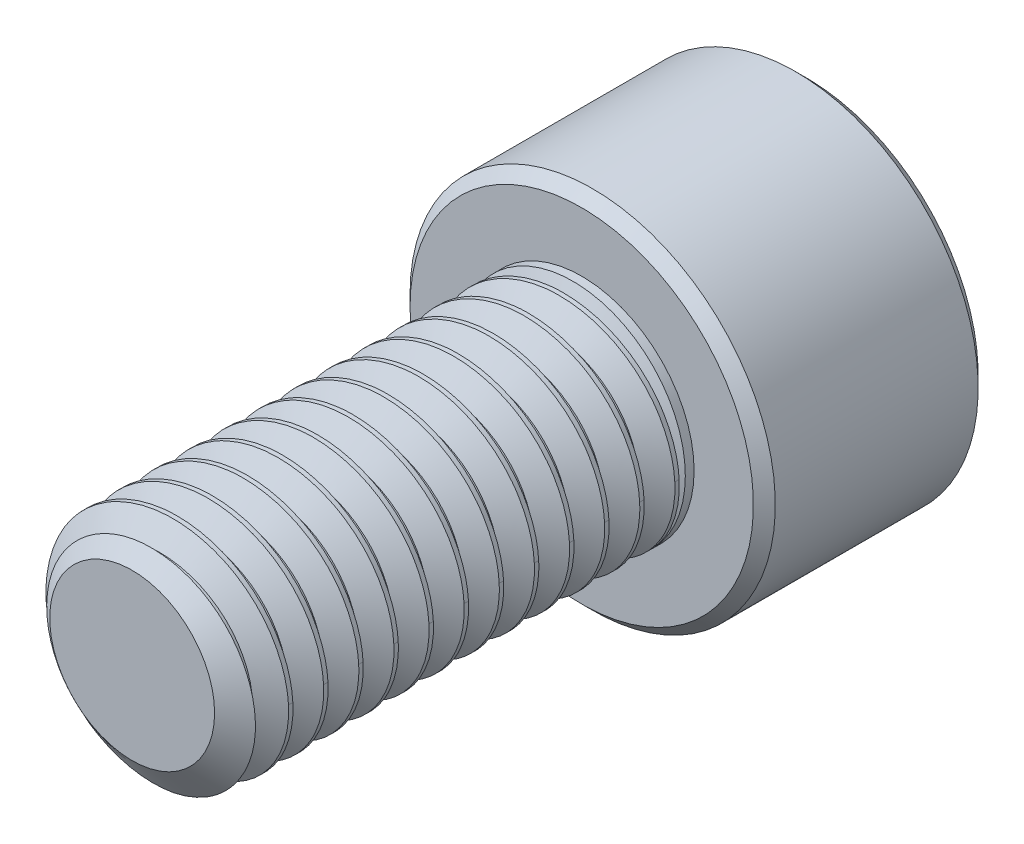
SolidWorks part; units mm, degrees
ref_plane "Front Plane" through (0, 0, 0) normal (0, 0, 1) x (1, 0, 0)
ref_plane "Top Plane" through (0, 0, 0) normal (0, 1, 0) x (1, 0, 0)
ref_plane "Right Plane" through (0, 0, 0) normal (1, 0, 0) x (0, 0, -1)
sketch "Sketch1" plane through (0, 0, 0) normal (0, 0, 1) x (1, 0, 0)
  circle A0 centre (0, 0) radius 4
  dimension "OD" = 8
extrude "Extrude1" add sketch "Sketch1" against normal blind 16
sketch "Sketch2" plane through (0, 0, 0) normal (0, 0, 1) x (1, 0, 0)
  circle A0 centre (0, 0) radius 4 construction
  circle A1 centre (0, 0) radius 4
curve "Helix/Spiral1" pitch 1.25 height 17.25 turns 13.8 parameters "pitch"=1.25
sketch "Sketch3" plane through (0, 0, 0) normal (1, 0, 0) x (0, 0, -1)
  line L0 (-1.0938, 4) -> (-0.625, 3.1881)
  line L1 (-0.625, 3.1881) -> (-0.4688, 3.1881)
  line L2 (-0.4688, 3.1881) -> (0, 4)
  line L3 (-1.0938, 4) -> (0, 4)
  line L4 (-0.5469, 4) -> (-0.5469, 3.1881) construction
  line L5 (-0.8594, 3.5941) -> (-0.2344, 3.5941) construction
  line L6 (0, 4) -> (0, -4) construction
  line L7 (0, -4) -> (16, -4) construction
  point P11 (5.625, -4)
  dimension "D1" = 0.1562
  dimension "D2" = 0.625
  dimension "D3" = 60
  dimension "D4" = 5.625
sweep "Cut-Sweep1" cut profiles "Sketch3" path "Helix/Spiral1"
sketch "Sketch4" plane through (0, 0, 0) normal (1, 0, 0) x (0, 0, -1)
  line L0 (0.7464, 4) -> (0, 2.9341)
  line L1 (0, 2.9341) -> (0, 4)
  line L2 (0.7464, 4) -> (0, 4)
  line L3 (-1.0938, 4) -> (0, 4) construction
  line L4 (0, 0) -> (7.0209, 0) construction
  dimension "D1" = 55
  dimension "D2" = 0.254
revolve "Cut-Revolve1" cut sketch "Sketch4" angle 360 about L4
sketch "Sketch5" plane through (0, 0, 0) normal (1, 0, 0) x (0, 0, -1)
  line L0 (16, -3.6352) -> (16, -0.9564) construction
  line L1 (16, 4) -> (0.1203, 4)
  line L2 (16, 4) -> (16, 0)
  line L3 (16, 0) -> (0.0001, 0)
  line L4 (0.0001, 3.6698) -> (0.0001, 0)
  line L5 (0.1203, 4) -> (0.0001, 3.6698)
  line L6 (0, 0) -> (9.9695, 0) construction
  point P3 (0.0001, 4)
  point P10 (0.0001, 4)
  dimension "D1" = 0.3302
  dimension "Thread min" = 0.0001
  dimension "D3" = 20
revolve "partially thread" [suppressed] add sketch "Sketch5" angle 360 about L6
sketch "Sketch6" plane through (0, 0, -16) normal (0, 0, -1) x (-1, 0, 0)
  circle A0 centre (0, 0) radius 6.5
  dimension "head dia" = 13
extrude "Extrude2" add sketch "Sketch6" along normal blind 8
sketch "Sketch7" plane through (0, 0, -24) normal (0, 0, -1) x (-1, 0, 0)
  line L1 (0, 3.4641) -> (-3, 1.7321)
  line L2 (-3, 1.7321) -> (-3, -1.7321)
  line L3 (-3, -1.7321) -> (0, -3.4641)
  line L4 (0, -3.4641) -> (3, -1.7321)
  line L5 (3, -1.7321) -> (3, 1.7321)
  line L6 (3, 1.7321) -> (0, 3.4641)
  circle A0 centre (0, 0) radius 3 construction
  dimension "hex dia" = 6
extrude "Cut-Extrude1" cut sketch "Sketch7" against normal blind 4.5
sketch "Sketch8" plane through (0, 0, -24) normal (0, 0, -1) x (-1, 0, 0)
  circle A0 centre (0, 0) radius 3.4641
extrude "Cut-Extrude2" cut sketch "Sketch8" against normal through all draft 45
chamfer "Chamfer1" distance 0.39 angle 45 2 edges at (-6.5, 0, -24) (-6.5, 0, -16)
sketch "Sketch9" plane through (0, 0, 0) normal (1, 0, 0) x (0, 0, -1)
  line L0 (0, 4) -> (0, -4) construction
  line L1 (6.875, 4) -> (6.875, -4) construction
  dimension "D1" = 6.875
sketch "Sketch10" plane through (0, 0, 0) normal (1, 0, 0) x (0, 0, -1)
  line L0 (16, 4) -> (16, 0)
  line L1 (16, 4) -> (15.6875, 4)
  line L2 (15.6875, 4) -> (14.0306, 0)
  line L3 (16, 0) -> (14.0306, 0)
  line L4 (16, 6.11) -> (16, -6.11) construction
  dimension "D1" = 22.5
  dimension "D2" = 0.3125
revolve "Revolve1" add sketch "Sketch10" angle 360 about L3
equation "\"D3@Helix/Spiral1\" = \"screw length@Extrude1\"+\"pitch@Helix/Spiral1\""
equation "\"D1@Sketch3\" = \"pitch@Helix/Spiral1\"*.125"
equation "\"D2@Sketch3\" = \"pitch@Helix/Spiral1\"*.5"
equation "\"D1@Cut-Extrude1\" = \"hex dia@Sketch7\"*.75"
equation "\"D1@Chamfer1\" = \"head dia@Sketch6\"*.03"
equation "\"D1@Sketch9\" = \"pitch@Helix/Spiral1\"*5.5"
equation "\"D2@Sketch10\" = \"pitch@Helix/Spiral1\"*.25"
equation "\"D4@Sketch3\" = \"pitch@Helix/Spiral1\"*4.50"
